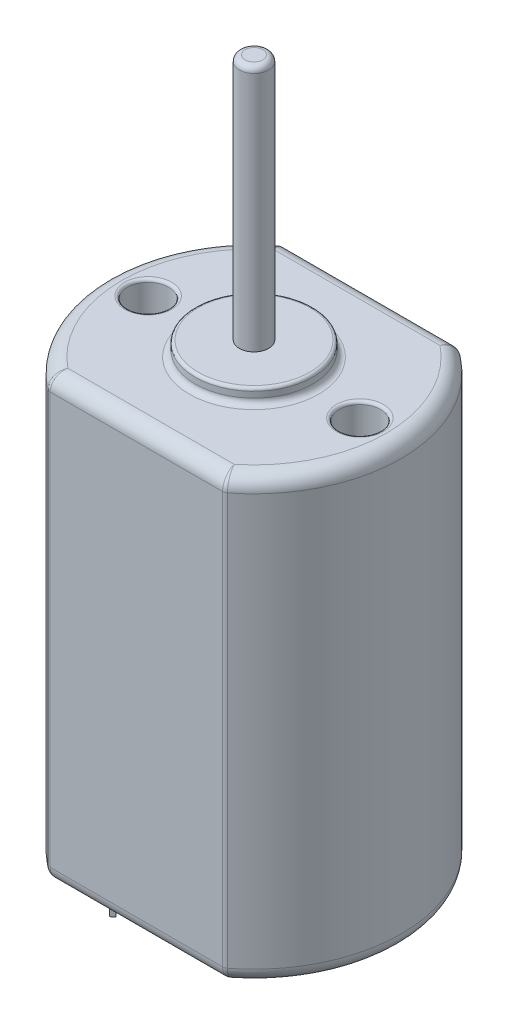
SolidWorks part; units mm, degrees
ref_plane "Front" through (0, 0, 0) normal (0, 0, 1) x (1, 0, 0)
ref_plane "Top" through (0, 0, 0) normal (0, 1, 0) x (1, 0, 0)
ref_plane "Right" through (0, 0, 0) normal (1, 0, 0) x (0, 0, -1)
sketch "Sketch1" plane through (0, 0, 0) normal (0, 1, 0) x (1, 0, 0)
  line L0 (-3, 4) -> (3, 4)
  line L1 (-3, -4) -> (3, -4)
  arc A2 (-3, 4) -> (-3, -4) centre (0, 0) ccw
  arc A3 (3, 4) -> (3, -4) centre (0, 0) cw
extrude "Boss-Extrude1" add sketch "Sketch1" along normal blind 15 contours L0 A3 L1 A2
fillet "Fillet1" radius 0.2 4 edges at (3, 7.5, 4) (-3, 7.5, 4) (3, 7.5, -4) (-3, 7.5, -4)
fillet "Fillet2" radius 0.5 16 edges at (2.9971, 0, -3.9893) (0, 0, -4) (-2.9971, 0, -3.9893) (-5, 0, 0) (-2.9971, 0, 3.9893) (0, 0, 4) (2.9971, 0, 3.9893) (5, 0, 0) (-2.9971, 15, 3.9893) (-5, 15, 0) (-2.9971, 15, -3.9893) (0, 15, -4) (2.9971, 15, -3.9893) (5, 15, 0) (2.9971, 15, 3.9893) (0, 15, 4)
sketch "Sketch2" plane through (0, 15, 0) normal (0, 1, 0) x (1, 0, 0)
  circle A0 centre (0, 0) radius 2
extrude "Boss-Extrude2" add sketch "Sketch2" along normal blind 0.5 contours A0
fillet "Fillet3" radius 0.2 1 edges at (0, 15, 2)
fillet "Fillet4" radius 0.1 1 edges at (0, 15.5, 2)
sketch "Sketch3" plane through (0, 15.5, 0) normal (0, 1, 0) x (1, 0, 0)
  circle A0 centre (0, 0) radius 0.5
extrude "Boss-Extrude3" add sketch "Sketch3" along normal blind 8.4
fillet "Fillet5" radius 0.2 1 edges at (0, 23.9, 0.5)
sketch "Sketch5" plane through (0, 0, 0) normal (0, -1, 0) x (1, 0, 0)
  circle A0 centre (0, 0) radius 2
extrude "Boss-Extrude4" add sketch "Sketch5" along normal blind 1.2
fillet "Fillet6" radius 0.5 1 edges at (0, -1.2, -2)
sketch "Sketch6" plane through (0, 0, 0) normal (0, -1, 0) x (1, 0, 0)
  line L4 (-3.1685, 1.4429) -> (-3.2884, 1.533)
  line L10 (2.3881, -2.7316) -> (3.169, -1.4422)
  line L11 (2.3881, -2.7316) -> (2.2682, -2.6416)
  line L12 (3.169, -1.4422) -> (3.0491, -1.3521)
  line L13 (2.2682, -2.6416) -> (3.0491, -1.3521)
  line L14 (-3.2884, 1.533) -> (-2.2677, 2.6423)
  line L15 (-3.2884, 1.533) -> (-3.1685, 1.4429)
  line L16 (-2.2677, 2.6423) -> (-2.1477, 2.5522)
  line L17 (-3.1685, 1.4429) -> (-2.1477, 2.5522)
extrude "Boss-Extrude5" add sketch "Sketch6" along normal blind 1.3 contours L13 L11 L10 L12 | L4 L17 L16 L14 region at (-2.7181, 0, 2.0426) region at (2.7186, 0, -2.0419)
sketch "Sketch7" plane through (0, 15, 0) normal (0, 1, 0) x (1, 0, 0)
  circle A0 centre (3.6, 0) radius 0.7
  circle A1 centre (-3.6, 0) radius 0.7
extrude "Cut-Extrude1" cut sketch "Sketch7" against normal blind 2
fillet "Fillet7" radius 0.1 2 edges at (-3.6, 15, 0.7) (3.6, 15, 0.7)
